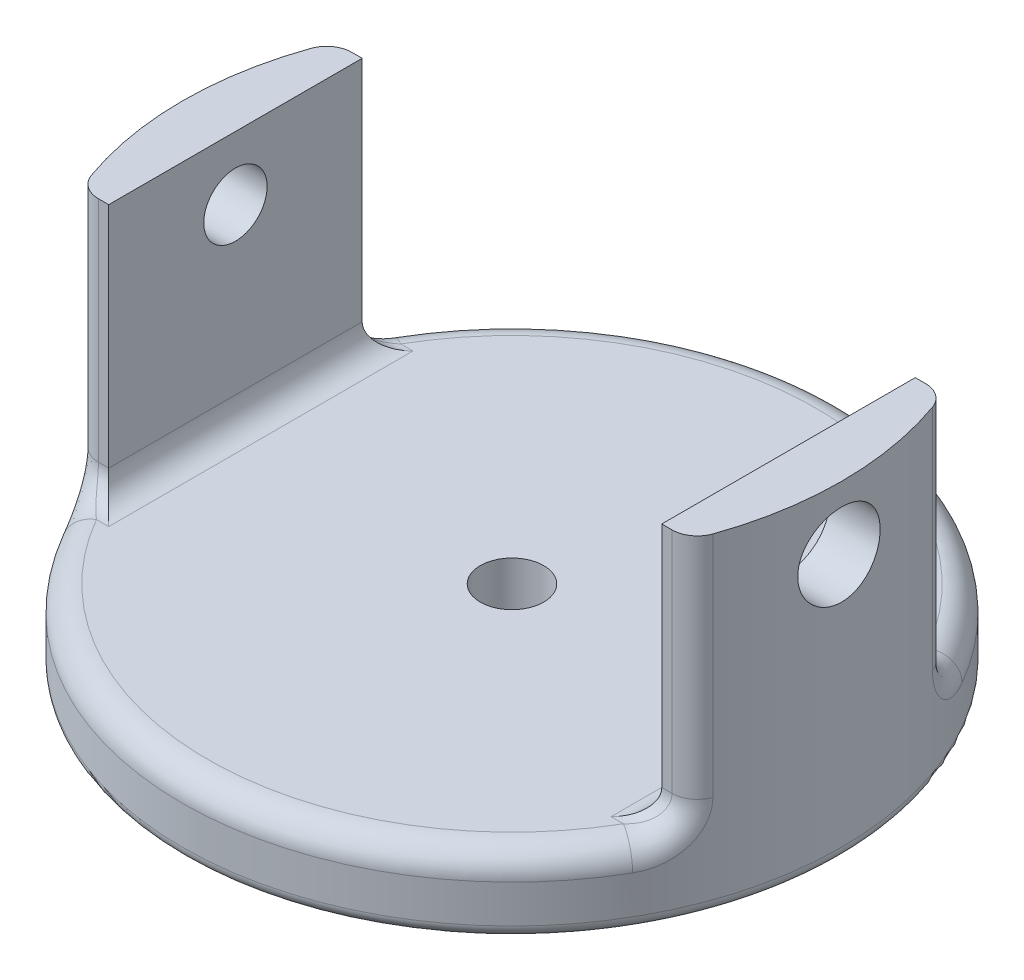
SolidWorks part; units mm, degrees
material "ABS"
ref_plane "Front Plane" through (0, 0, 0) normal (0, 0, 1) x (1, 0, 0)
ref_plane "Top Plane" through (0, 0, 0) normal (0, 1, 0) x (1, 0, 0)
ref_plane "Right Plane" through (0, 0, 0) normal (1, 0, 0) x (0, 0, -1)
sketch "Sketch1" plane through (0, 0, 0) normal (0, 1, 0) x (1, 0, 0)
  circle A0 centre (0, 0) radius 26
  dimension "D1" = 52
extrude "Boss-Extrude1" add sketch "Sketch1" along normal blind 6
fillet "Fillet1" radius 1 1 edges at (0, 0, 26)
sketch "Sketch2" plane through (0, 0, 0) normal (0, -1, 0) x (1, 0, 0)
  line L0 (0, 0) -> (0, 2.5) construction
  line L1 (0, 0) -> (0.7415, 2.3875) construction
  circle A40 centre (0, 0) radius 2.5
  dimension "D1" = 5
  dimension "D2" = 0.75
extrude "Cut-Extrude1" cut sketch "Sketch2" against normal through all
sketch "Sketch3" plane through (0, 6, 0) normal (0, 1, 0) x (1, 0, 0)
  line L0 (-21.8174, 10) -> (-21.8174, -10)
  line L1 (-29.9437, 0) -> (37.2142, 0) construction
  line L2 (0, 31.9815) -> (0, -33.8733) construction
  line L3 (-21.8174, 10) -> (-24, 10)
  line L4 (-21.8174, -10) -> (-24, -10)
  line L5 (21.8174, 10) -> (24, 10)
  line L6 (21.8174, -10) -> (24, -10)
  line L7 (21.8174, 10) -> (21.8174, -10)
  arc A0 (24, 10) -> (24, -10) centre (0, 0) cw
  circle A3 centre (0, 0) radius 26 construction
  arc A4 (-24, 10) -> (-24, -10) centre (0, 0) ccw
  point P10 (-21.8174, 0)
  dimension "D2" = 20
  dimension "D3" = 2.1826
  dimension "D4" = 2.1826
extrude "Boss-Extrude2" add sketch "Sketch3" along normal blind 20
fillet "Fillet3" radius 2 12 edges at (24, 16, -10) (-24, 16, -10) (-24, 16, 10) (24, 16, 10) (0, 6, -26) (0, 6, 26) (22.9087, 6, -10) (21.8174, 6, 0) (22.9087, 6, 10) (-22.9087, 6, -10) (-22.9087, 6, 10) (-21.8174, 6, 0)
sketch "Sketch5" plane through (-21.8174, 0, 0) normal (1, 0, 0) x (0, 0, -1)
  line L2 (-10, 21) -> (10, 21) construction
  line L3 (-10, 26) -> (-10, 8) construction
  line L4 (10, 26) -> (10, 8) construction
  line L5 (-10, 26) -> (10, 26) construction
  circle A80 centre (0, 21) radius 2.5
  dimension "D1" = 5
  dimension "D4" = 5
extrude "Cut-Extrude2" cut sketch "Sketch5" against normal through all
sketch "Sketch6" plane through (21.8174, 0, 0) normal (-1, 0, 0) x (0, 0, 1)
  line L0 (-10, 21) -> (10, 21) construction
  line L1 (-10, 26) -> (-10, 8) construction
  line L2 (10, 26) -> (10, 8) construction
  line L3 (-10, 26) -> (10, 26) construction
  circle A0 centre (0, 21) radius 3.25
  dimension "D2" = 6.5
  dimension "D1" = 5
extrude "Cut-Extrude3" cut sketch "Sketch6" against normal through all
